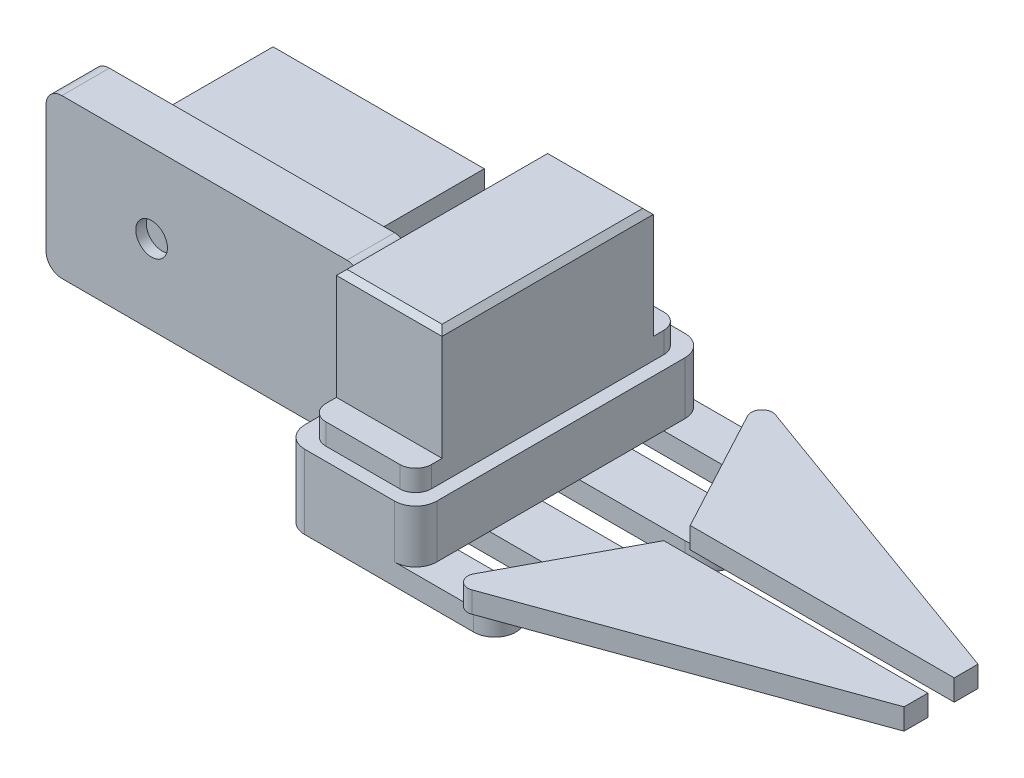
SolidWorks part; units mm, degrees
ref_plane "前视基准面" through (0, 0, 0) normal (0, 0, 1) x (1, 0, 0)
ref_plane "上视基准面" through (0, 0, 0) normal (0, 1, 0) x (1, 0, 0)
ref_plane "右视基准面" through (0, 0, 0) normal (1, 0, 0) x (0, 0, -1)
other "Configuration Table"
sketch "草图1" plane through (0, 0, 0) normal (0, 0, 1) x (1, 0, 0)
  line L1 (-30, -15) -> (30, -15)
  line L2 (-30, -15) -> (-30, 15)
  line L3 (-30, 15) -> (30, 15)
  line L4 (30, -15) -> (30, 15)
  line L5 (-30, -15) -> (30, 15) construction
  line L6 (-30, 15) -> (30, -15) construction
  point P0 (0, 0)
  dimension "D1" = 30
  dimension "D2" = 60
extrude "凸台-拉伸1" add sketch "草图1" along normal blind 9
sketch "草图2" plane through (0, -15, 0) normal (0, -1, 0) x (1, 0, 0)
  line L0 (-30, 9) -> (30, 9) construction
  line L1 (30, 24) -> (55, 24)
  line L2 (30, 24) -> (30, -31)
  line L3 (30, -31) -> (55, -31)
  line L4 (55, 24) -> (55, -31)
  line L5 (30, 9) -> (30, 0) construction
  dimension "D1" = 55
  dimension "D2" = 15
  dimension "D3" = 25
extrude "凸台-拉伸2" add sketch "草图2" against normal blind 10
sketch "草图3" plane through (0, -5, 0) normal (0, 1, 0) x (1, 0, 0)
  line L1 (32.5, 23.5) -> (52.5, 23.5)
  line L2 (32.5, 23.5) -> (32.5, -16.5)
  line L3 (32.5, -16.5) -> (52.5, -16.5)
  line L4 (52.5, 23.5) -> (52.5, -16.5)
  line L5 (30, 0) -> (30, 31) construction
  line L7 (30, 31) -> (55, 31) construction
  dimension "D1" = 20
  dimension "D2" = 40
  dimension "D3" = 2.5
  dimension "D4" = 7.5
  dimension "D5" = 31
extrude "凸台-拉伸3" add sketch "草图3" along normal blind 25
sketch "草图4" plane through (0, -5, 0) normal (0, 1, 0) x (1, 0, 0)
  line L0 (32.5, 23.5) -> (32.5, -16.5) construction
  line L1 (52.5, 23.5) -> (32.5, 23.5)
  line L2 (52.5, 23.5) -> (52.5, 28.5)
  line L3 (52.5, 28.5) -> (32.5, 28.5)
  line L4 (32.5, 23.5) -> (32.5, 28.5)
  line L5 (52.5, -16.5) -> (32.5, -16.5)
  line L6 (52.5, -16.5) -> (52.5, -21.5)
  line L7 (52.5, -21.5) -> (32.5, -21.5)
  line L8 (32.5, -16.5) -> (32.5, -21.5)
  dimension "D1" = 5
  dimension "D2" = 5
extrude "凸台-拉伸4" add sketch "草图4" along normal blind 4
fillet "圆角1" radius 4 4 edges at (30, -10, -31) (55, -10, -31) (30, -10, 24) (55, -10, 24)
fillet "圆角2" radius 3 4 edges at (32.5, -3, -28.5) (52.5, -3, -28.5) (52.5, -3, 21.5) (32.5, -3, 21.5)
fillet "圆角3" radius 3 3 edges at (-30, -15, 4.5) (-30, 15, 4.5) (30, 15, 4.5)
sketch "草图5" plane through (0, -15, 0) normal (0, -1, 0) x (1, 0, 0)
  line L0 (34, 24) -> (66, 24)
  line L1 (66, 16) -> (34, 16)
  line L2 (35, 10) -> (75, 10)
  line L3 (75, 0) -> (35, 0)
  line L4 (-27, 9) -> (30, 9) construction
  line L5 (30, 20) -> (30, 9) construction
  arc A2 (34, 24) -> (34, 16) centre (34, 20) ccw
  arc A3 (66, 24) -> (66, 16) centre (66, 20) cw
  arc A4 (35, 10) -> (35, 0) centre (35, 5) ccw
  arc A5 (75, 10) -> (75, 0) centre (75, 5) cw
  dimension "D1" = 4
  dimension "D2" = 40
  dimension "D3" = 10
  dimension "D4" = 4
  dimension "D5" = 5
  dimension "D6" = 50
extrude "凸台-拉伸5" add sketch "草图5" along normal blind 4
ref_plane "基准面1" through (0, 0, -3.5) normal (0, 0, -1) x (-1, 0, 0)
mirror "镜向1" about plane through (0, 0, -3.5) normal (0, 0, -1) of "凸台-拉伸5"
sketch "草图6" plane through (0, -15, 0) normal (0, 1, 0) x (1, 0, 0)
  line L0 (62, 34) -> (77, 6)
  line L1 (66, 31) -> (51, 31) construction
  line L2 (77, 6) -> (127, 6)
  line L3 (127, 6) -> (127, 10.5)
  line L4 (127, 10.5) -> (62, 34)
  line L5 (55, 27) -> (55, -20) construction
  line L6 (55, 7) -> (75, 7) construction
  dimension "D1" = 72
  dimension "D2" = 50
  dimension "D3" = 65
  dimension "D4" = 4.5
  dimension "D5" = 1
  dimension "D6" = 3
extrude "凸台-拉伸6" add sketch "草图6" along normal blind 4
mirror "镜向2" about plane through (0, 0, -3.5) normal (0, 0, -1) of "凸台-拉伸6"
fillet "圆角4" radius 2 2 edges at (62, -13, -34) (62, -13, 27)
chamfer "倒角1" distance 1 angle 45 4 edges at (42.5, 20, 16.5) (32.5, 20, -3.5) (52.5, 20, -3.5) (42.5, 20, -23.5)
sketch "草图7" plane through (0, 0, 0) normal (0, 0, -1) x (-1, 0, 0)
  line L1 (-20, -10) -> (20, -10)
  line L2 (-20, -10) -> (-20, 10)
  line L3 (-20, 10) -> (20, 10)
  line L4 (20, -10) -> (20, 10)
  line L5 (-20, -10) -> (20, 10) construction
  line L6 (-20, 10) -> (20, -10) construction
  point P0 (0, 0)
  dimension "D1" = 20
  dimension "D2" = 40
extrude "凸台-拉伸7" add sketch "草图7" along normal blind 25
sketch "草图8" plane through (0, 0, 0) normal (0, 0, -1) x (-1, 0, 0)
  line L0 (-20, -10) -> (20, -10) construction
  line L1 (20, 10) -> (25, 10)
  line L2 (20, 10) -> (20, -10)
  line L3 (20, -10) -> (25, -10)
  line L4 (25, 10) -> (25, -10)
  line L5 (-20, 10) -> (-25, 10)
  line L6 (-20, 10) -> (-20, -10)
  line L7 (-20, -10) -> (-25, -10)
  line L8 (-25, 10) -> (-25, -10)
  dimension "D1" = 5
  dimension "D2" = 5
extrude "凸台-拉伸8" add sketch "草图8" along normal blind 4
chamfer "倒角2" distance 1 angle 45 4 edges at (0, -10, -25) (20, 0, -25) (0, 10, -25) (-20, 0, -25)
fillet "圆角6" radius 2 4 edges at (25, 10, -2) (25, -10, -2) (-25, -10, -2) (-25, 10, -2)
sketch "草图9" plane through (0, 0, 9) normal (0, 0, 1) x (1, 0, 0)
  line L0 (-30, 12) -> (-30, -12) construction
  circle A0 centre (-10, 0) radius 3
  dimension "D1" = 6
  dimension "D2" = 20
extrude "切除-拉伸1" cut sketch "草图9" against normal blind 2
